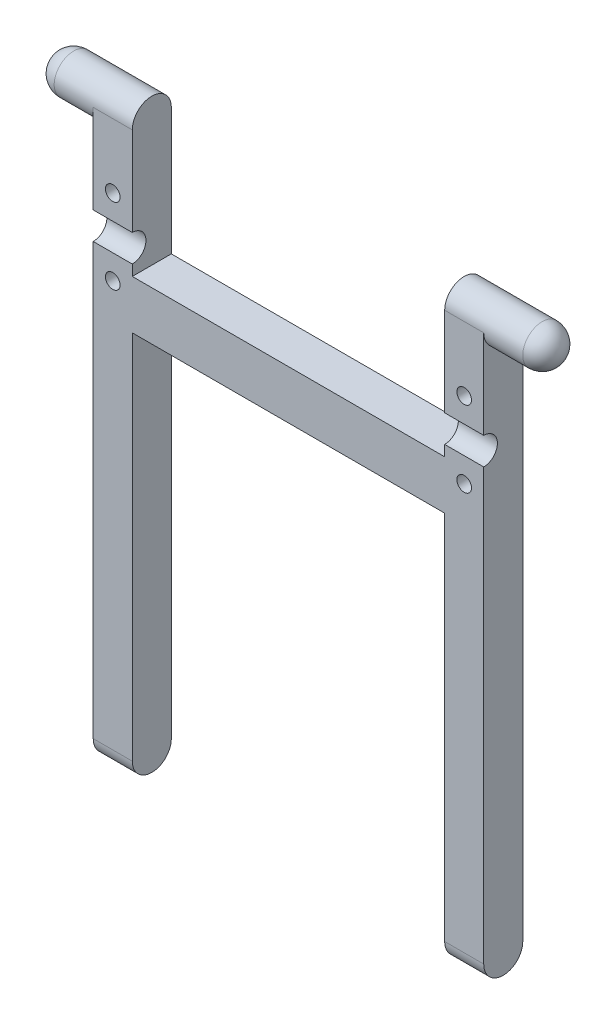
SolidWorks part; units mm, degrees
ref_plane "Alzado" through (0, 0, 0) normal (0, 0, 1) x (1, 0, 0)
ref_plane "Planta" through (0, 0, 0) normal (0, 1, 0) x (1, 0, 0)
ref_plane "Vista lateral" through (0, 0, 0) normal (1, 0, 0) x (0, 0, -1)
sketch "Croquis1" plane through (0, 0, 0) normal (0, 0, 1) x (1, 0, 0)
  line L0 (-96.2848, 9.613) -> (-96.2848, -70.387)
  line L1 (-104.2848, 49.613) -> (-96.2848, 49.613)
  line L2 (-104.2848, 49.613) -> (-104.2848, -70.387)
  line L3 (-104.2848, -70.387) -> (-96.2848, -70.387)
  line L4 (-96.2848, 49.613) -> (-96.2848, 19.613)
  line L5 (-64.2848, 49.613) -> (-64.2848, 19.613) construction
  line L6 (-32.2848, 19.613) -> (-96.2848, 19.613)
  line L7 (-96.2848, 9.613) -> (-32.2848, 9.613)
  line L8 (-32.2848, 49.613) -> (-32.2848, 19.613)
  line L9 (-24.2848, -70.387) -> (-32.2848, -70.387)
  line L10 (-24.2848, 49.613) -> (-24.2848, -70.387)
  line L11 (-24.2848, 49.613) -> (-32.2848, 49.613)
  line L12 (-32.2848, 9.613) -> (-32.2848, -70.387)
  point P10 (-64.2848, 9.613)
  dimension "D1" = 120
  dimension "D2" = 8
  dimension "D3" = 32
  dimension "D4" = 30
  dimension "D5" = 10
extrude "Saliente-Extruir1" add sketch "Croquis1" along normal blind 8
fillet "Redondeo1" radius 4 8 edges at (-100.2848, -70.387, 0) (-28.2848, -70.387, 0) (-28.2848, 49.613, 8) (-28.2848, 49.613, 0) (-100.2848, 49.613, 0) (-100.2848, 49.613, 8) (-28.2848, -70.387, 8) (-100.2848, -70.387, 8)
sketch "Croquis2" plane through (-104.2848, 0, 0) normal (-1, 0, 0) x (0, 0, 1)
  line L0 (4, 49.613) -> (4, 45.613) construction
ref_plane "Plano3" through (0, 0, 4) normal (0, 0, 1) x (1, 0, 0)
sketch "Croquis4" plane through (0, 0, 4) normal (0, 0, 1) x (1, 0, 0)
  line L0 (-104.2848, 49.613) -> (-112.2848, 49.613)
  line L1 (-104.2848, 45.613) -> (-116.2848, 45.613)
  line L2 (-104.2848, 49.613) -> (-104.2848, 45.613)
  arc A0 (-116.2848, 45.613) -> (-112.2848, 49.613) centre (-112.2848, 45.613) cw
revolve "Revolución3" add sketch "Croquis4" angle 360 about L1
ref_plane "Plano4" through (-64.2848, 0, 0) normal (-1, 0, 0) x (0, 0, 1)
mirror "Simetría1" about plane through (-64.2848, 0, 0) normal (-1, 0, 0) of "Revolución3"
sketch "Croquis6" plane through (-104.2848, 0, 0) normal (-1, 0, 0) x (0, 0, 1)
  line L0 (8, 45.613) -> (8, -66.387) construction
  circle A0 centre (8, 24.613) radius 2.8
  dimension "D1" = 25
extrude "Cortar-Extruir1" cut sketch "Croquis6" against normal up to vertex (80 mm away) up to point (-24.2848, -66.387, 8)
sketch "Croquis7" plane through (0, 0, 8) normal (0, 0, 1) x (1, 0, 0)
  line L0 (-104.2848, 21.813) -> (-96.2848, 21.813) construction
  circle A0 centre (-100.2848, 16.813) radius 1.5
  circle A1 centre (-28.2848, 16.813) radius 1.5
  circle A2 centre (-28.2848, 32.413) radius 1.5
  circle A3 centre (-100.2848, 32.413) radius 1.5
  dimension "D1" = 5
  dimension "D2" = 2
  dimension "D3" = 2
extrude "Cortar-Extruir2" cut sketch "Croquis7" against normal up to vertex (8 mm away) up to point (-104.2848, -66.387, 0)
sketch "Croquis8" plane through (0, 0, 0) normal (0, 0, -1) x (-1, 0, 0)
  line L0 (103.7489, 16.813) -> (102.0168, 19.813)
  line L1 (31.7489, 16.813) -> (30.0168, 19.813)
  line L2 (30.0168, 19.813) -> (26.5527, 19.813)
  line L3 (26.5527, 19.813) -> (24.8207, 16.813)
  line L4 (24.8207, 16.813) -> (26.5527, 13.813)
  line L5 (26.5527, 13.813) -> (30.0168, 13.813)
  line L6 (30.0168, 13.813) -> (31.7489, 16.813)
  line L7 (102.0168, 19.813) -> (98.5527, 19.813)
  line L8 (98.5527, 19.813) -> (96.8207, 16.813)
  line L9 (96.8207, 16.813) -> (98.5527, 13.813)
  line L10 (98.5527, 13.813) -> (102.0168, 13.813)
  line L11 (102.0168, 13.813) -> (103.7489, 16.813)
  line L12 (103.7489, 32.413) -> (102.0168, 35.413)
  line L13 (102.0168, 35.413) -> (98.5527, 35.413)
  line L14 (98.5527, 35.413) -> (96.8207, 32.413)
  line L15 (96.8207, 32.413) -> (98.5527, 29.413)
  line L16 (98.5527, 29.413) -> (102.0168, 29.413)
  line L17 (102.0168, 29.413) -> (103.7489, 32.413)
  line L18 (31.7489, 32.413) -> (30.0168, 35.413)
  line L19 (30.0168, 35.413) -> (26.5527, 35.413)
  line L20 (26.5527, 35.413) -> (24.8207, 32.413)
  line L21 (24.8207, 32.413) -> (26.5527, 29.413)
  line L22 (26.5527, 29.413) -> (30.0168, 29.413)
  line L23 (30.0168, 29.413) -> (31.7489, 32.413)
  circle A0 centre (28.2848, 16.813) radius 3 construction
  circle A1 centre (100.2848, 16.813) radius 3 construction
  circle A2 centre (100.2848, 32.413) radius 3 construction
  circle A3 centre (28.2848, 32.413) radius 3 construction
  point P1 (28.2848, 13.813)
  dimension "D1" = 6
  dimension "D2" = 2
  dimension "D3" = 2
extrude "Cortar-Extruir3" cut sketch "Croquis8" against normal blind 3
sketch "Croquis9" plane through (0, 0, 8) normal (0, 0, 1) x (1, 0, 0)
  line L0 (-104.2848, 45.613) -> (-104.2848, 27.413) construction
  line L1 (-104.2848, 37.413) -> (-96.2848, 37.413)
  line L2 (-104.2848, 37.413) -> (-104.2848, 11.813)
  line L3 (-104.2848, 11.813) -> (-96.2848, 11.813)
  line L4 (-96.2848, 37.413) -> (-96.2848, 11.813)
  line L5 (-96.2848, -66.387) -> (-96.2848, 9.613) construction
  circle A0 centre (-100.2848, 32.413) radius 1.5
  circle A1 centre (-100.2848, 16.813) radius 1.5
  dimension "D1" = 5
  dimension "D2" = 5
